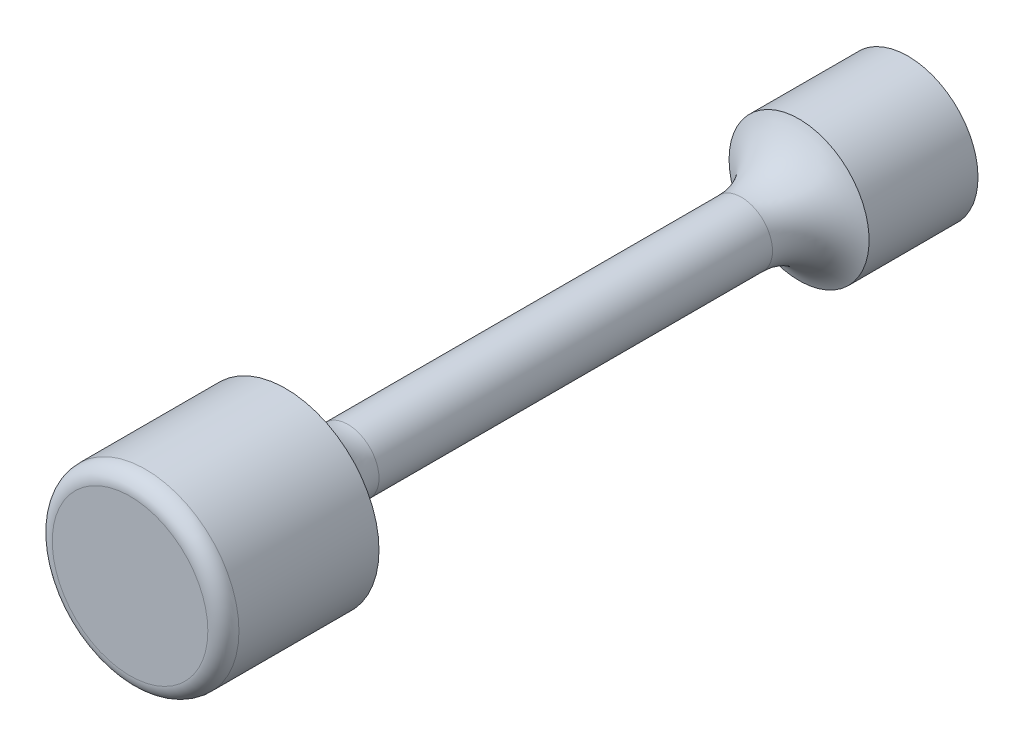
SolidWorks part; units mm, degrees
ref_plane "Front Plane" through (0, 0, 0) normal (0, 0, 1) x (1, 0, 0)
ref_plane "Top Plane" through (0, 0, 0) normal (0, 1, 0) x (1, 0, 0)
ref_plane "Right Plane" through (0, 0, 0) normal (1, 0, 0) x (0, 0, -1)
sketch "草图1" plane through (0, 0, 0) normal (0, 0, 1) x (1, 0, 0)
  circle A0 centre (0, 0) radius 2.25
  dimension "D1" = 4.5
extrude "凸台-拉伸2" add sketch "草图1" along normal blind 20
sketch "草图7" plane through (0, 0, 0) normal (0, 0, 1) x (1, 0, 0)
  line L1 (1.2, -1.2) -> (-1.2, -1.2)
  line L2 (1.2, -1.2) -> (1.2, 1.2)
  line L3 (1.2, 1.2) -> (-1.2, 1.2)
  line L4 (-1.2, -1.2) -> (-1.2, 1.2)
  line L5 (1.2, -1.2) -> (-1.2, 1.2) construction
  line L6 (1.2, 1.2) -> (-1.2, -1.2) construction
  point P0 (0, 0)
  dimension "D1" = 2.4
  dimension "D2" = 2.4
extrude "切除-拉伸3" cut sketch "草图7" along normal blind 2.5 from surface starting at face at (2.25, 0, 0)
sketch "草图9" plane through (0, 0, 20) normal (0, 0, 1) x (1, 0, 0)
  circle A0 centre (0, 0) radius 3
extrude "凸台-拉伸4" add sketch "草图9" along normal blind 5
sketch "草图10" plane through (0, 0, 25) normal (0, 0, 1) x (1, 0, 0)
  line L1 (2, -2) -> (-2, -2)
  line L2 (2, -2) -> (2, 2)
  line L3 (2, 2) -> (-2, 2)
  line L4 (-2, -2) -> (-2, 2)
  line L5 (2, -2) -> (-2, 2) construction
  line L6 (2, 2) -> (-2, -2) construction
  point P0 (0, 0)
  dimension "D1" = 4
  dimension "D2" = 4
sketch "草图12" plane through (0, 0, 0) normal (0, 0, -1) x (-1, 0, 0)
  circle A0 centre (0, 0) radius 1
extrude "切除-拉伸4" cut sketch "草图12" along normal blind 16.5 from surface flip side to cut starting at face at (2.25, 0, 20)
fillet "圆角2" radius 2 2 edges at (1, 0, 20) (1, 0, 3.5)
fillet "圆角3" radius 0.5 1 edges at (3, 0, 25)
